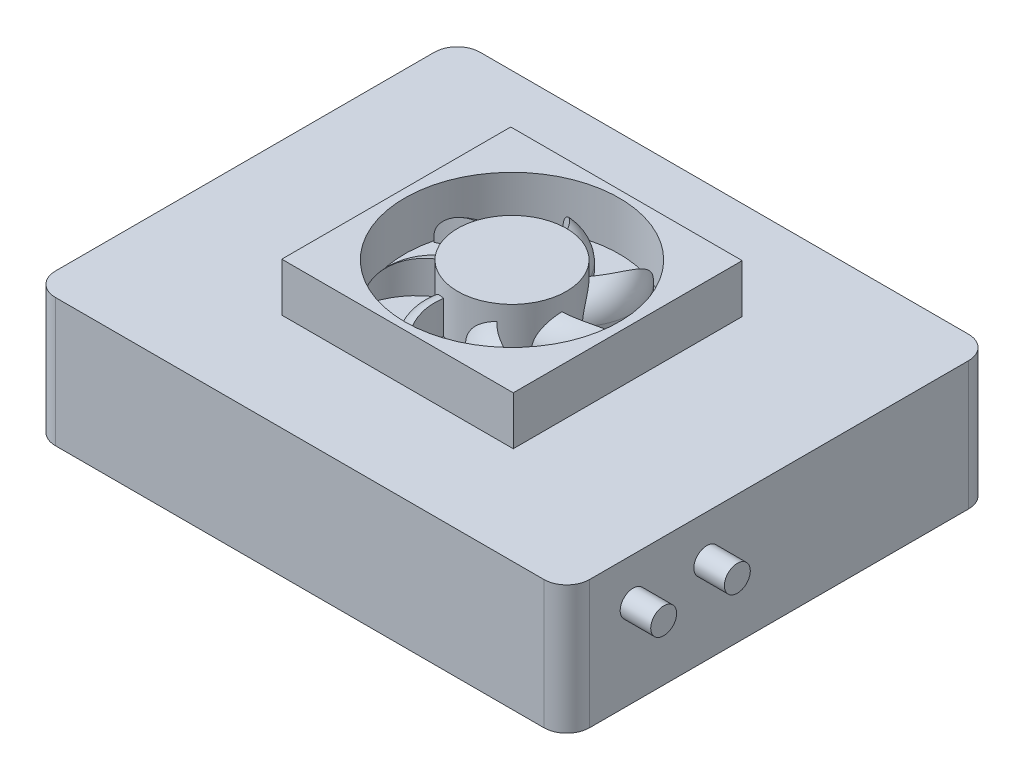
SolidWorks part; units mm, degrees
ref_plane "Front Plane" through (0, 0, 0) normal (0, 0, 1) x (1, 0, 0)
ref_plane "Top Plane" through (0, 0, 0) normal (0, 1, 0) x (1, 0, 0)
ref_plane "Right Plane" through (0, 0, 0) normal (1, 0, 0) x (0, 0, -1)
sketch "Sketch1" plane through (0, 0, 0) normal (0, 1, 0) x (1, 0, 0)
  line L1 (35, -27.825) -> (-35, -27.825)
  line L2 (35, -27.825) -> (35, 27.825)
  line L3 (35, 27.825) -> (-35, 27.825)
  line L4 (-35, -27.825) -> (-35, 27.825)
  line L5 (35, -27.825) -> (-35, 27.825) construction
  line L6 (35, 27.825) -> (-35, -27.825) construction
  point P0 (0, 0)
  dimension "D1" = 70
  dimension "D2" = 55.65
extrude "Boss-Extrude1" add sketch "Sketch1" along normal blind 16.83
sketch "Sketch2" plane through (0, 0, 0) normal (0, 1, 0) x (1, 0, 0)
  line L1 (15.165, -15) -> (-15.165, -15)
  line L2 (15.165, -15) -> (15.165, 15)
  line L3 (15.165, 15) -> (-15.165, 15)
  line L4 (-15.165, -15) -> (-15.165, 15)
  line L5 (15.165, -15) -> (-15.165, 15) construction
  line L6 (15.165, 15) -> (-15.165, -15) construction
  point P0 (0, 0)
  dimension "D1" = 30.33
  dimension "D2" = 30
extrude "Boss-Extrude2" add sketch "Sketch2" along normal blind 6.35 from surface contours L4 L3 L2 L1 starting at face at (0, 16.83, 0)
sketch "Sketch3" plane through (0, 23.18, 0) normal (0, 1, 0) x (1, 0, 0)
  circle A0 centre (0, 0) radius 14.055
extrude "Boss-Extrude3" add sketch "Sketch3" against normal blind 6.35
sketch "Sketch4" plane through (0, 23.18, 0) normal (0, 1, 0) x (1, 0, 0)
  circle A0 centre (0, 0) radius 14.055
  dimension "D1" = 28.11
extrude "Cut-Extrude1" cut sketch "Sketch4" against normal blind 6.35
sketch "Sketch5" plane through (0, 0, 0) normal (1, 0, 0) x (0, 0, -1)
  line L0 (27.825, 16.83) -> (27.825, 0) construction
  line L1 (23.495, 8.86) -> (14.055, 8.86)
  line L2 (23.495, 8.86) -> (23.495, 4)
  line L3 (23.495, 4) -> (14.055, 4)
  line L4 (14.055, 8.86) -> (14.055, 4)
  line L5 (23.495, 8.86) -> (14.055, 4) construction
  line L6 (23.495, 4) -> (14.055, 8.86) construction
  line L7 (27.825, 0) -> (-27.825, 0) construction
  point P0 (18.775, 6.43)
  point P7 (23.495, 6.43)
  dimension "D1" = 4.86
  dimension "D2" = 9.44
  dimension "D3" = 4.33
  dimension "D4" = 4
extrude "Boss-Extrude4" add sketch "Sketch5" against normal blind 6.76 from surface contours L2 L3 L4 L1 starting at face at (-35, 8.415, 0)
sketch "Sketch6" plane through (35, 0, 0) normal (1, 0, 0) x (0, 0, -1)
  line L0 (-27.825, 16.83) -> (27.825, 16.83) construction
  circle A0 centre (-19.1254, 11.29) radius 1.7
  circle A1 centre (-9.4754, 11.29) radius 1.7
  dimension "D1" = 5.54
  dimension "D2" = 9.65
extrude "Boss-Extrude5" add sketch "Sketch6" along normal blind 4
fillet "Fillet1" radius 3 4 edges at (-35, 8.415, -27.825) (35, 8.415, -27.825) (35, 8.415, 27.825) (-35, 8.415, 27.825)
sketch "Sketch7" plane through (0, 16.83, 0) normal (0, 1, 0) x (1, 0, 0)
  circle A0 centre (0, 0) radius 7.14
  dimension "D1" = 14.28
extrude "Boss-Extrude6" add sketch "Sketch7" along normal blind 6.35
sketch "Sketch11" plane through (0, 16.83, 0) normal (0, 1, 0) x (1, 0, 0)
  arc A0 (7.1161, -0.5832) -> (6.1449, -3.6359) centre (0, 0) cw
  circle A1 centre (0, 0) radius 7.14 construction
  circle A2 centre (0, 0) radius 7.14 construction
  arc A3 (6.1449, -3.6359) -> (13.5166, 2.9135) centre (6.556, 3.3246) ccw
  arc A4 (7.1161, -0.5832) -> (13.5166, 2.9135) centre (6.6644, 7.8498) ccw
extrude "Boss-Extrude7" add sketch "Sketch11" along normal blind 4.35
fillet "Fillet3" radius 3.5 1 edges at (11.1872, 21.18, 1.8879)
pattern_circular "CirPattern11" count 7 over 360 about axis through (0, 23.18, 0) along (0, 1, 0) of "Boss-Extrude7"
fillet "Fillet4" radius 3.5 6 edges at (5.4991, 21.18, 9.9236) (-4.33, 21.18, 10.4866) (-10.8984, 21.18, 3.153) (-9.2602, 21.18, -6.5549) (-0.6488, 21.18, -11.3268) (8.4511, 21.18, -7.5694)
